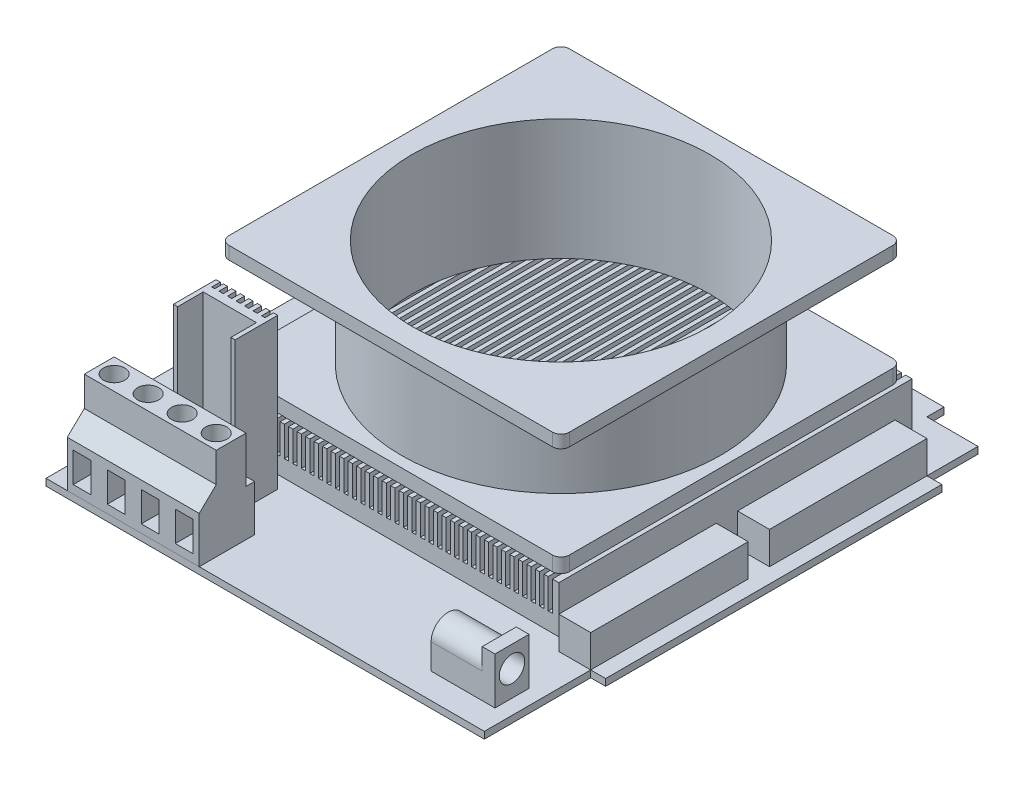
SolidWorks part; units mm, degrees
ref_plane "前视基准面" through (0, 0, 0) normal (0, 0, 1) x (1, 0, 0)
ref_plane "上视基准面" through (0, 0, 0) normal (0, 1, 0) x (1, 0, 0)
ref_plane "右视基准面" through (0, 0, 0) normal (1, 0, 0) x (0, 0, -1)
sketch "草图2" plane through (0, 0, 0) normal (0, 1, 0) x (1, 0, 0)
  line L0 (0, 84.4726) -> (0, -75.2088) construction
  line L1 (-51.5, -58) -> (51.5, -58)
  line L2 (-51.5, -58) -> (-51.5, 58)
  line L3 (-51.5, 58) -> (51.5, 58)
  line L4 (51.5, -58) -> (51.5, 58)
  line L5 (-51.5, -58) -> (51.5, 58) construction
  line L6 (-51.5, 58) -> (51.5, -58) construction
  line L7 (-39.5, 62) -> (39.5, 62)
  line L8 (-39.5, 62) -> (-39.5, -58)
  line L9 (-39.5, -58) -> (39.5, -58)
  line L10 (39.5, 62) -> (39.5, -58)
  line L11 (-55, 46) -> (55, 46)
  line L12 (-55, 46) -> (-55, -33)
  line L13 (-55, -33) -> (55, -33)
  line L14 (55, 46) -> (55, -33)
  point P0 (0, 0)
  point P10 (0, -58)
  point P11 (0, -58)
  point P18 (0, -33)
  dimension "D1" = 103
  dimension "D2" = 116
  dimension "D3" = 79
  dimension "D4" = 120
  dimension "D5" = 110
  dimension "D6" = 79
  dimension "D7" = 25
extrude "凸台-拉伸1" add sketch "草图2" along normal blind 1.6 contours L13 L2 L1 L8 | L12 L13 L2 L11 | L2 L11 L8 L3 | L10 L7 L8 L3 | L10 L11 L4 L3 | L14 L11 L4 L13 | L13 L10 L1 L4 | L13 L8 L1 L10 | L8 L13 L10 L11 | L10 L13 L4 L11 | L2 L13 L8 L11 | L8 L11 L10 L3 region at (-45.5, 0, 45.5) region at (0, 0, 45.5) region at (-53.25, 0, -6.5) region at (-45.5, 0, -6.5) region at (45.5, 0, 45.5) region at (0, 0, -6.5) region at (-45.5, 0, -52) region at (45.5, 0, -6.5) region at (0, 0, -52) region at (53.25, 0, -6.5) region at (45.5, 0, -52) region at (0, 0, -60)
sketch "草图3" plane through (0, 1.6, 0) normal (0, 1, 0) x (1, 0, 0)
  line L0 (0, 64.6269) -> (0, -63.4056) construction
  line L1 (-51.5, -33) -> (-44, -33)
  line L2 (-51.5, -33) -> (-51.5, 46)
  line L3 (-51.5, 46) -> (-44, 46)
  line L4 (-44, -33) -> (-44, 46)
  line L6 (51.5, 46) -> (44, 46)
  line L7 (44, -33) -> (44, 46)
  line L8 (51.5, -33) -> (44, -33)
  line L9 (51.5, -33) -> (51.5, 46)
  dimension "D1" = 7.5
extrude "凸台-拉伸2" add sketch "草图3" along normal blind 7.6 separate body
sketch "草图4" plane through (0, 1.6, 0) normal (0, 1, 0) x (1, 0, 0)
  line L0 (-39.5, 62) -> (39.5, 62) construction
  line L1 (-41, -30) -> (41, -30)
  line L2 (-41, -30) -> (-41, 53)
  line L3 (-41, 53) -> (41, 53)
  line L4 (41, -30) -> (41, 53)
  line L5 (-41, -30) -> (41, 53) construction
  line L6 (-41, 53) -> (41, -30) construction
  line L7 (0, 70.9867) -> (0, -89.7313) construction
  point P0 (0, 11.5)
  point P5 (0, 53)
  dimension "D1" = 82
  dimension "D2" = 83
  dimension "D3" = 92
extrude "凸台-拉伸3" add sketch "草图4" along normal blind 11
sketch "草图5" plane through (0, 12.6, 0) normal (0, 1, 0) x (1, 0, 0)
  line L0 (-41, 53) -> (41, -30) construction
  line L1 (-38, -28.5) -> (38, -28.5)
  line L2 (-40, -26.5) -> (-40, 49.5)
  line L3 (-38, 51.5) -> (38, 51.5)
  line L4 (40, -26.5) -> (40, 49.5)
  line L5 (-40, -28.5) -> (40, 51.5) construction
  line L6 (-40, 51.5) -> (40, -28.5) construction
  line L7 (-41, -30) -> (41, 53) construction
  arc A0 (-40, -26.5) -> (-38, -28.5) centre (-38, -26.5) ccw
  arc A1 (38, -28.5) -> (40, -26.5) centre (38, -26.5) ccw
  arc A2 (40, 49.5) -> (38, 51.5) centre (38, 49.5) ccw
  arc A3 (-40, 49.5) -> (-38, 51.5) centre (-38, 49.5) cw
  point P0 (0, 11.5)
  point P13 (0, 0)
  point P14 (0, 11.5)
  dimension "D3" = 2
  dimension "D1" = 80
  dimension "D2" = 80
extrude "凸台-拉伸4" add sketch "草图5" along normal blind 28.4 separate body
sketch "草图8" plane through (0, 0, 30) normal (0, 0, 1) x (1, 0, 0)
  line L1 (38.5, 13.6) -> (39.5, 13.6)
  line L2 (38.5, 13.6) -> (38.5, 5.6)
  line L3 (38.5, 5.6) -> (39.5, 5.6)
  line L4 (39.5, 13.6) -> (39.5, 5.6)
  line L6 (-41, 1.6) -> (41, 1.6) construction
  line L7 (41, 12.6) -> (41, 1.6) construction
  line L8 (36.5, 13.6) -> (36.5, 5.6)
  line L9 (36.5, 13.6) -> (37.5, 13.6)
  line L10 (37.5, 13.6) -> (37.5, 5.6)
  line L11 (36.5, 5.6) -> (37.5, 5.6)
  line L12 (34.5, 13.6) -> (34.5, 5.6)
  line L13 (34.5, 13.6) -> (35.5, 13.6)
  line L14 (35.5, 13.6) -> (35.5, 5.6)
  line L15 (34.5, 5.6) -> (35.5, 5.6)
  line L16 (32.5, 13.6) -> (32.5, 5.6)
  line L17 (32.5, 13.6) -> (33.5, 13.6)
  line L18 (33.5, 13.6) -> (33.5, 5.6)
  line L19 (32.5, 5.6) -> (33.5, 5.6)
  line L20 (30.5, 13.6) -> (30.5, 5.6)
  line L21 (30.5, 13.6) -> (31.5, 13.6)
  line L22 (31.5, 13.6) -> (31.5, 5.6)
  line L23 (30.5, 5.6) -> (31.5, 5.6)
  line L24 (28.5, 13.6) -> (28.5, 5.6)
  line L25 (28.5, 13.6) -> (29.5, 13.6)
  line L26 (29.5, 13.6) -> (29.5, 5.6)
  line L27 (28.5, 5.6) -> (29.5, 5.6)
  line L28 (26.5, 13.6) -> (26.5, 5.6)
  line L29 (26.5, 13.6) -> (27.5, 13.6)
  line L30 (27.5, 13.6) -> (27.5, 5.6)
  line L31 (26.5, 5.6) -> (27.5, 5.6)
  line L32 (24.5, 13.6) -> (24.5, 5.6)
  line L33 (24.5, 13.6) -> (25.5, 13.6)
  line L34 (25.5, 13.6) -> (25.5, 5.6)
  line L35 (24.5, 5.6) -> (25.5, 5.6)
  line L36 (22.5, 13.6) -> (22.5, 5.6)
  line L37 (22.5, 13.6) -> (23.5, 13.6)
  line L38 (23.5, 13.6) -> (23.5, 5.6)
  line L39 (22.5, 5.6) -> (23.5, 5.6)
  line L40 (20.5, 13.6) -> (20.5, 5.6)
  line L41 (20.5, 13.6) -> (21.5, 13.6)
  line L42 (21.5, 13.6) -> (21.5, 5.6)
  line L43 (20.5, 5.6) -> (21.5, 5.6)
  line L44 (18.5, 13.6) -> (18.5, 5.6)
  line L45 (18.5, 13.6) -> (19.5, 13.6)
  line L46 (19.5, 13.6) -> (19.5, 5.6)
  line L47 (18.5, 5.6) -> (19.5, 5.6)
  line L48 (16.5, 13.6) -> (16.5, 5.6)
  line L49 (16.5, 13.6) -> (17.5, 13.6)
  line L50 (17.5, 13.6) -> (17.5, 5.6)
  line L51 (16.5, 5.6) -> (17.5, 5.6)
  line L52 (14.5, 13.6) -> (14.5, 5.6)
  line L53 (14.5, 13.6) -> (15.5, 13.6)
  line L54 (15.5, 13.6) -> (15.5, 5.6)
  line L55 (14.5, 5.6) -> (15.5, 5.6)
  line L56 (12.5, 13.6) -> (12.5, 5.6)
  line L57 (12.5, 13.6) -> (13.5, 13.6)
  line L58 (13.5, 13.6) -> (13.5, 5.6)
  line L59 (12.5, 5.6) -> (13.5, 5.6)
  line L60 (10.5, 13.6) -> (10.5, 5.6)
  line L61 (10.5, 13.6) -> (11.5, 13.6)
  line L62 (11.5, 13.6) -> (11.5, 5.6)
  line L63 (10.5, 5.6) -> (11.5, 5.6)
  line L64 (8.5, 13.6) -> (8.5, 5.6)
  line L65 (8.5, 13.6) -> (9.5, 13.6)
  line L66 (9.5, 13.6) -> (9.5, 5.6)
  line L67 (8.5, 5.6) -> (9.5, 5.6)
  line L68 (6.5, 13.6) -> (6.5, 5.6)
  line L69 (6.5, 13.6) -> (7.5, 13.6)
  line L70 (7.5, 13.6) -> (7.5, 5.6)
  line L71 (6.5, 5.6) -> (7.5, 5.6)
  line L72 (4.5, 13.6) -> (4.5, 5.6)
  line L73 (4.5, 13.6) -> (5.5, 13.6)
  line L74 (5.5, 13.6) -> (5.5, 5.6)
  line L75 (4.5, 5.6) -> (5.5, 5.6)
  line L76 (2.5, 13.6) -> (2.5, 5.6)
  line L77 (2.5, 13.6) -> (3.5, 13.6)
  line L78 (3.5, 13.6) -> (3.5, 5.6)
  line L79 (2.5, 5.6) -> (3.5, 5.6)
  line L80 (0.5, 13.6) -> (0.5, 5.6)
  line L81 (0.5, 13.6) -> (1.5, 13.6)
  line L82 (1.5, 13.6) -> (1.5, 5.6)
  line L83 (0.5, 5.6) -> (1.5, 5.6)
  line L84 (-1.5, 13.6) -> (-1.5, 5.6)
  line L85 (-1.5, 13.6) -> (-0.5, 13.6)
  line L86 (-0.5, 13.6) -> (-0.5, 5.6)
  line L87 (-1.5, 5.6) -> (-0.5, 5.6)
  line L88 (-3.5, 13.6) -> (-3.5, 5.6)
  line L89 (-3.5, 13.6) -> (-2.5, 13.6)
  line L90 (-2.5, 13.6) -> (-2.5, 5.6)
  line L91 (-3.5, 5.6) -> (-2.5, 5.6)
  line L92 (-5.5, 13.6) -> (-5.5, 5.6)
  line L93 (-5.5, 13.6) -> (-4.5, 13.6)
  line L94 (-4.5, 13.6) -> (-4.5, 5.6)
  line L95 (-5.5, 5.6) -> (-4.5, 5.6)
  line L96 (-7.5, 13.6) -> (-7.5, 5.6)
  line L97 (-7.5, 13.6) -> (-6.5, 13.6)
  line L98 (-6.5, 13.6) -> (-6.5, 5.6)
  line L99 (-7.5, 5.6) -> (-6.5, 5.6)
  line L100 (-9.5, 13.6) -> (-9.5, 5.6)
  line L101 (-9.5, 13.6) -> (-8.5, 13.6)
  line L102 (-8.5, 13.6) -> (-8.5, 5.6)
  line L103 (-9.5, 5.6) -> (-8.5, 5.6)
  line L104 (-11.5, 13.6) -> (-11.5, 5.6)
  line L105 (-11.5, 13.6) -> (-10.5, 13.6)
  line L106 (-10.5, 13.6) -> (-10.5, 5.6)
  line L107 (-11.5, 5.6) -> (-10.5, 5.6)
  line L108 (-13.5, 13.6) -> (-13.5, 5.6)
  line L109 (-13.5, 13.6) -> (-12.5, 13.6)
  line L110 (-12.5, 13.6) -> (-12.5, 5.6)
  line L111 (-13.5, 5.6) -> (-12.5, 5.6)
  line L112 (-15.5, 13.6) -> (-15.5, 5.6)
  line L113 (-15.5, 13.6) -> (-14.5, 13.6)
  line L114 (-14.5, 13.6) -> (-14.5, 5.6)
  line L115 (-15.5, 5.6) -> (-14.5, 5.6)
  line L116 (-17.5, 13.6) -> (-17.5, 5.6)
  line L117 (-17.5, 13.6) -> (-16.5, 13.6)
  line L118 (-16.5, 13.6) -> (-16.5, 5.6)
  line L119 (-17.5, 5.6) -> (-16.5, 5.6)
  line L120 (-19.5, 13.6) -> (-19.5, 5.6)
  line L121 (-19.5, 13.6) -> (-18.5, 13.6)
  line L122 (-18.5, 13.6) -> (-18.5, 5.6)
  line L123 (-19.5, 5.6) -> (-18.5, 5.6)
  line L124 (-21.5, 13.6) -> (-21.5, 5.6)
  line L125 (-21.5, 13.6) -> (-20.5, 13.6)
  line L126 (-20.5, 13.6) -> (-20.5, 5.6)
  line L127 (-21.5, 5.6) -> (-20.5, 5.6)
  line L128 (-23.5, 13.6) -> (-23.5, 5.6)
  line L129 (-23.5, 13.6) -> (-22.5, 13.6)
  line L130 (-22.5, 13.6) -> (-22.5, 5.6)
  line L131 (-23.5, 5.6) -> (-22.5, 5.6)
  line L132 (-25.5, 13.6) -> (-25.5, 5.6)
  line L133 (-25.5, 13.6) -> (-24.5, 13.6)
  line L134 (-24.5, 13.6) -> (-24.5, 5.6)
  line L135 (-25.5, 5.6) -> (-24.5, 5.6)
  line L136 (-27.5, 13.6) -> (-27.5, 5.6)
  line L137 (-27.5, 13.6) -> (-26.5, 13.6)
  line L138 (-26.5, 13.6) -> (-26.5, 5.6)
  line L139 (-27.5, 5.6) -> (-26.5, 5.6)
  line L140 (-29.5, 13.6) -> (-29.5, 5.6)
  line L141 (-29.5, 13.6) -> (-28.5, 13.6)
  line L142 (-28.5, 13.6) -> (-28.5, 5.6)
  line L143 (-29.5, 5.6) -> (-28.5, 5.6)
  line L144 (-31.5, 13.6) -> (-31.5, 5.6)
  line L145 (-31.5, 13.6) -> (-30.5, 13.6)
  line L146 (-30.5, 13.6) -> (-30.5, 5.6)
  line L147 (-31.5, 5.6) -> (-30.5, 5.6)
  line L148 (-33.5, 13.6) -> (-33.5, 5.6)
  line L149 (-33.5, 13.6) -> (-32.5, 13.6)
  line L150 (-32.5, 13.6) -> (-32.5, 5.6)
  line L151 (-33.5, 5.6) -> (-32.5, 5.6)
  line L152 (-35.5, 13.6) -> (-35.5, 5.6)
  line L153 (-35.5, 13.6) -> (-34.5, 13.6)
  line L154 (-34.5, 13.6) -> (-34.5, 5.6)
  line L155 (-35.5, 5.6) -> (-34.5, 5.6)
  line L156 (-37.5, 13.6) -> (-37.5, 5.6)
  line L157 (-37.5, 13.6) -> (-36.5, 13.6)
  line L158 (-36.5, 13.6) -> (-36.5, 5.6)
  line L159 (-37.5, 5.6) -> (-36.5, 5.6)
  line L160 (-39.5, 13.6) -> (-39.5, 5.6)
  line L161 (-39.5, 13.6) -> (-38.5, 13.6)
  line L162 (-38.5, 13.6) -> (-38.5, 5.6)
  line L163 (-39.5, 5.6) -> (-38.5, 5.6)
  line L164 (-41.5, 13.6) -> (-41.5, 5.6)
  line L165 (-41.5, 13.6) -> (-40.5, 13.6)
  line L166 (-40.5, 13.6) -> (-40.5, 5.6)
  line L167 (-41.5, 5.6) -> (-40.5, 5.6)
  line L168 (-43.5, 13.6) -> (-43.5, 5.6)
  line L169 (-43.5, 13.6) -> (-42.5, 13.6)
  line L170 (-42.5, 13.6) -> (-42.5, 5.6)
  line L171 (-43.5, 5.6) -> (-42.5, 5.6)
  line L172 (-45.5, 13.6) -> (-45.5, 5.6)
  line L173 (-45.5, 13.6) -> (-44.5, 13.6)
  line L174 (-44.5, 13.6) -> (-44.5, 5.6)
  line L175 (-45.5, 5.6) -> (-44.5, 5.6)
  line L176 (-47.5, 13.6) -> (-47.5, 5.6)
  line L177 (-47.5, 13.6) -> (-46.5, 13.6)
  line L178 (-46.5, 13.6) -> (-46.5, 5.6)
  line L179 (-47.5, 5.6) -> (-46.5, 5.6)
  line L180 (-49.5, 13.6) -> (-49.5, 5.6)
  line L181 (-49.5, 13.6) -> (-48.5, 13.6)
  line L182 (-48.5, 13.6) -> (-48.5, 5.6)
  line L183 (-49.5, 5.6) -> (-48.5, 5.6)
  line L184 (-51.5, 13.6) -> (-51.5, 5.6)
  line L185 (-51.5, 13.6) -> (-50.5, 13.6)
  line L186 (-50.5, 13.6) -> (-50.5, 5.6)
  line L187 (-51.5, 5.6) -> (-50.5, 5.6)
  line L188 (-53.5, 13.6) -> (-53.5, 5.6)
  line L189 (-53.5, 13.6) -> (-52.5, 13.6)
  line L190 (-52.5, 13.6) -> (-52.5, 5.6)
  line L191 (-53.5, 5.6) -> (-52.5, 5.6)
  line L192 (-55.5, 13.6) -> (-55.5, 5.6)
  line L193 (-55.5, 13.6) -> (-54.5, 13.6)
  line L194 (-54.5, 13.6) -> (-54.5, 5.6)
  line L195 (-55.5, 5.6) -> (-54.5, 5.6)
  line L196 (-57.5, 13.6) -> (-57.5, 5.6)
  line L197 (-57.5, 13.6) -> (-56.5, 13.6)
  line L198 (-56.5, 13.6) -> (-56.5, 5.6)
  line L199 (-57.5, 5.6) -> (-56.5, 5.6)
  line L200 (-59.5, 13.6) -> (-59.5, 5.6)
  line L201 (-59.5, 13.6) -> (-58.5, 13.6)
  line L202 (-58.5, 13.6) -> (-58.5, 5.6)
  line L203 (-59.5, 5.6) -> (-58.5, 5.6)
  dimension "D1" = 1
  dimension "D2" = 8
  dimension "D3" = 4
  dimension "D4" = 1.5
  dimension "D5" = 50
extrude "切除-拉伸2" cut sketch "草图8" against normal blind 115.4
sketch "草图6" plane through (0, 1.6, 0) normal (0, 1, 0) x (1, 0, 0)
  line L0 (-51.5, -58) -> (-51.5, -33) construction
  line L1 (-46.5, -45) -> (-15.5, -45)
  line L2 (-46.5, -45) -> (-46.5, -58)
  line L3 (-46.5, -58) -> (-15.5, -58)
  line L4 (-15.5, -45) -> (-15.5, -58)
  line L5 (-46.5, -45) -> (-15.5, -58) construction
  line L6 (-46.5, -58) -> (-15.5, -45) construction
  line L7 (-51.5, -58) -> (51.5, -58) construction
  point P0 (-31, -51.5)
  dimension "D1" = 31
  dimension "D2" = 13
  dimension "D3" = 5
extrude "凸台-拉伸5" add sketch "草图6" along normal blind 21.7 separate body
sketch "草图7" plane through (0, 1.6, 0) normal (0, 1, 0) x (1, 0, 0)
  line L1 (-36.5502, -43) -> (-22.0502, -43)
  line L2 (-36.5502, -43) -> (-36.5502, -33)
  line L3 (-36.5502, -33) -> (-22.0502, -33)
  line L4 (-22.0502, -43) -> (-22.0502, -33)
  line L5 (-36.5502, -43) -> (-22.0502, -33) construction
  line L6 (-36.5502, -33) -> (-22.0502, -43) construction
  line L8 (-51.5, -58) -> (51.5, -58) construction
  line L9 (-35.5502, -43) -> (-35.5502, -37)
  line L10 (-35.5502, -37) -> (-23.0502, -37)
  line L11 (-23.0502, -37) -> (-23.0502, -43)
  line L12 (-32.8502, -35) -> (-32.8502, -33)
  line L13 (-35.5502, -33) -> (-23.0502, -33)
  line L14 (-35.5502, -33) -> (-35.5502, -35)
  line L15 (-35.5502, -35) -> (-23.0502, -35)
  line L16 (-23.0502, -33) -> (-23.0502, -35)
  line L17 (-34.8502, -35) -> (-33.8502, -35)
  line L18 (-34.8502, -35) -> (-34.8502, -33)
  line L19 (-34.8502, -33) -> (-33.8502, -33)
  line L20 (-33.8502, -35) -> (-33.8502, -33)
  line L21 (-32.8502, -35) -> (-31.8502, -35)
  line L22 (-31.8502, -35) -> (-31.8502, -33)
  line L23 (-32.8502, -33) -> (-31.8502, -33)
  line L24 (-30.8502, -35) -> (-30.8502, -33)
  line L25 (-30.8502, -35) -> (-29.8502, -35)
  line L26 (-29.8502, -35) -> (-29.8502, -33)
  line L27 (-30.8502, -33) -> (-29.8502, -33)
  line L28 (-28.8502, -35) -> (-28.8502, -33)
  line L29 (-28.8502, -35) -> (-27.8502, -35)
  line L30 (-27.8502, -35) -> (-27.8502, -33)
  line L31 (-28.8502, -33) -> (-27.8502, -33)
  line L32 (-26.8502, -35) -> (-26.8502, -33)
  line L33 (-26.8502, -35) -> (-25.8502, -35)
  line L34 (-25.8502, -35) -> (-25.8502, -33)
  line L35 (-26.8502, -33) -> (-25.8502, -33)
  line L36 (-24.8502, -35) -> (-24.8502, -33)
  line L37 (-24.8502, -35) -> (-23.8502, -35)
  line L38 (-23.8502, -35) -> (-23.8502, -33)
  line L39 (-24.8502, -33) -> (-23.8502, -33)
  point P0 (-29.3002, -38)
  dimension "D1" = 14.5
  dimension "D2" = 10
  dimension "D3" = 25
  dimension "D4" = 6
  dimension "D5" = 1
  dimension "D6" = 1
  dimension "D7" = 2
  dimension "D8" = 1
  dimension "D9" = 0.7
  dimension "D10" = 6
extrude "凸台-拉伸6" add sketch "草图7" along normal blind 35.4 separate body contours L10 L11 L1 L4 L3 L2 L9 | L18 L17 L20 L19 | L12 L23 L22 L21 | L24 L27 L26 L25 | L28 L31 L30 L29 | L32 L35 L34 L33 | L36 L39 L38 L37 region at (-29.3002, 1.6, 36.8889)
ref_plane "基准面1" through (0, 38, 0) normal (0, 1, 0) x (1, 0, 0)
sketch "草图9" plane through (0, 38, 0) normal (0, 1, 0) x (1, 0, 0)
  line L0 (-40, 11.5) -> (40, 11.5) construction
  line L1 (-55.6802, 63.1307) -> (75.1309, 63.1307)
  line L2 (-55.6802, 63.1307) -> (-55.6802, -42.1381)
  line L3 (-55.6802, -42.1381) -> (75.1309, -42.1381)
  line L4 (75.1309, 63.1307) -> (75.1309, -42.1381)
  line L5 (-40, 49.5) -> (-40, -26.5) construction
  line L6 (40, -26.5) -> (40, 49.5) construction
  circle A0 centre (0, 11.5) radius 37.5
  dimension "D1" = 75
extrude "切除-拉伸3" cut sketch "草图9" against normal blind 22 contours L4 L1 L2 L3 A0 region at (9.7253, 38, -61.4516)
sketch "草图10" plane through (0, 41, 0) normal (0, 1, 0) x (1, 0, 0)
  line L0 (-40, 11.5) -> (40, 11.5) construction
  line L1 (-40, 49.5) -> (-40, -26.5) construction
  line L2 (40, -26.5) -> (40, 49.5) construction
  circle A0 centre (0, 11.5) radius 35
  dimension "D1" = 70
extrude "切除-拉伸4" cut sketch "草图10" against normal blind 45
sketch "草图11" plane through (0, 9.2, 0) normal (0, 1, 0) x (1, 0, 0)
  line L0 (-51.5, 6.5) -> (51.5, 6.5) construction
  line L1 (-51.5, 46) -> (-51.5, -33) construction
  line L2 (51.5, -33) -> (51.5, 46) construction
  line L4 (-51.5, 4) -> (51.5, 4)
  line L5 (-51.5, 4) -> (-51.5, 9)
  line L6 (-51.5, 9) -> (51.5, 9)
  line L7 (51.5, 4) -> (51.5, 9)
  point P10 (0, 0)
  point P11 (51.5, 6.5)
  point P17 (0, 0)
  dimension "D1" = 5
extrude "切除-拉伸5" cut sketch "草图11" against normal blind 25
sketch "草图13" plane through (-46.5, 0, 0) normal (-1, 0, 0) x (0, 0, 1)
  line L0 (45, 23.3) -> (45, 1.6) construction
  line L1 (45, 12.45) -> (47, 12.45)
  line L2 (45, 12.45) -> (45, 23.3)
  line L3 (45, 23.3) -> (47, 23.3)
  line L4 (47, 12.45) -> (47, 23.3)
  line L5 (45, 23.3) -> (58, 23.3) construction
  line L6 (58, 23.3) -> (54, 23.3)
  line L7 (54, 23.3) -> (54, 16.3)
  line L8 (54, 16.3) -> (58, 12.45)
  line L9 (58, 23.3) -> (58, 1.6) construction
  line L10 (58, 12.45) -> (58, 23.3)
  dimension "D1" = 2
  dimension "D2" = 7
  dimension "D3" = 4
extrude "切除-拉伸8" cut sketch "草图13" against normal blind 45
sketch "草图14" plane through (0, 23.3, 0) normal (0, 1, 0) x (1, 0, 0)
  line L0 (-46.5, -47) -> (-46.5, -54) construction
  circle A0 centre (-43, -50.5) radius 2.5
  circle A1 centre (-35, -50.5) radius 2.5
  circle A2 centre (-27, -50.5) radius 2.5
  circle A3 centre (-19, -50.5) radius 2.5
  dimension "D1" = 5
  dimension "D3" = 3.5
  dimension "D2" = 4
extrude "切除-拉伸9" cut sketch "草图14" against normal blind 15
sketch "草图15" plane through (0, 0, 58) normal (0, 0, 1) x (1, 0, 0)
  line L0 (-46.5, 12.45) -> (-46.5, 1.6) construction
  line L1 (-45.1, 3.525) -> (-40.9, 3.525)
  line L2 (-45.1, 3.525) -> (-45.1, 10.525)
  line L3 (-45.1, 10.525) -> (-40.9, 10.525)
  line L4 (-40.9, 3.525) -> (-40.9, 10.525)
  line L5 (-45.1, 3.525) -> (-40.9, 10.525) construction
  line L6 (-45.1, 10.525) -> (-40.9, 3.525) construction
  line L7 (-37.1, 3.525) -> (-37.1, 10.525)
  line L8 (-37.1, 3.525) -> (-32.9, 3.525)
  line L9 (-32.9, 3.525) -> (-32.9, 10.525)
  line L10 (-37.1, 10.525) -> (-32.9, 10.525)
  line L11 (-29.1, 3.525) -> (-29.1, 10.525)
  line L12 (-29.1, 3.525) -> (-24.9, 3.525)
  line L13 (-24.9, 3.525) -> (-24.9, 10.525)
  line L14 (-29.1, 10.525) -> (-24.9, 10.525)
  line L15 (-21.1, 3.525) -> (-21.1, 10.525)
  line L16 (-21.1, 3.525) -> (-16.9, 3.525)
  line L17 (-16.9, 3.525) -> (-16.9, 10.525)
  line L18 (-21.1, 10.525) -> (-16.9, 10.525)
  point P0 (-43, 7.025)
  dimension "D1" = 3.5
  dimension "D2" = 4.2
  dimension "D3" = 7
  dimension "D4" = 4
extrude "切除-拉伸10" cut sketch "草图15" against normal blind 12
ref_plane "基准面2" through (48, 0, 0) normal (1, 0, 0) x (0, 0, -1)
sketch "草图16" plane through (48, 0, 0) normal (1, 0, 0) x (0, 0, -1)
  line L0 (-33, 1.6) -> (4, 1.6) construction
  line L1 (-52, 12.6) -> (-44, 12.6)
  line L2 (-52, 12.6) -> (-52, 1.6)
  line L3 (-52, 1.6) -> (-44, 1.6)
  line L4 (-44, 12.6) -> (-44, 1.6)
  line L5 (-52, 12.6) -> (-44, 1.6) construction
  line L6 (-52, 1.6) -> (-44, 12.6) construction
  line L7 (-58, 12.45) -> (-58, 1.6) construction
  point P0 (-48, 7.1)
  dimension "D1" = 11
  dimension "D2" = 8
  dimension "D3" = 6
extrude "凸台-拉伸7" add sketch "草图16" against normal blind 15 separate body
sketch "草图17" plane through (33, 0, 0) normal (-1, 0, 0) x (0, 0, 1)
  line L0 (58, 1.6) -> (33, 1.6) construction
  line L1 (44, 12.6) -> (52, 12.6)
  line L2 (44, 12.6) -> (44, 1.6)
  line L3 (44, 1.6) -> (52, 1.6)
  line L4 (52, 12.6) -> (52, 1.6)
  circle A0 centre (48, 7.6) radius 4
  line M5 (44, 12.6) -> (44, 1.6)
  line M8 (52, 12.6) -> (44, 12.6)
  dimension "D2" = 8
  dimension "D1" = 8
  dimension "D3" = 5
extrude "切除-拉伸11" cut sketch "草图17" against normal blind 12 contours A0 L4 M8 M5 region at (33, 12.5057, 48)
sketch "草图18" plane through (48, 0, 0) normal (1, 0, 0) x (0, 0, -1)
  line L0 (-44, 12.6) -> (-52, 12.6) construction
  circle A0 centre (-48, 7.6) radius 3
  point P2 (0, 0)
  dimension "D1" = 6
  dimension "D2" = 5
extrude "切除-拉伸12" cut sketch "草图18" against normal blind 12
